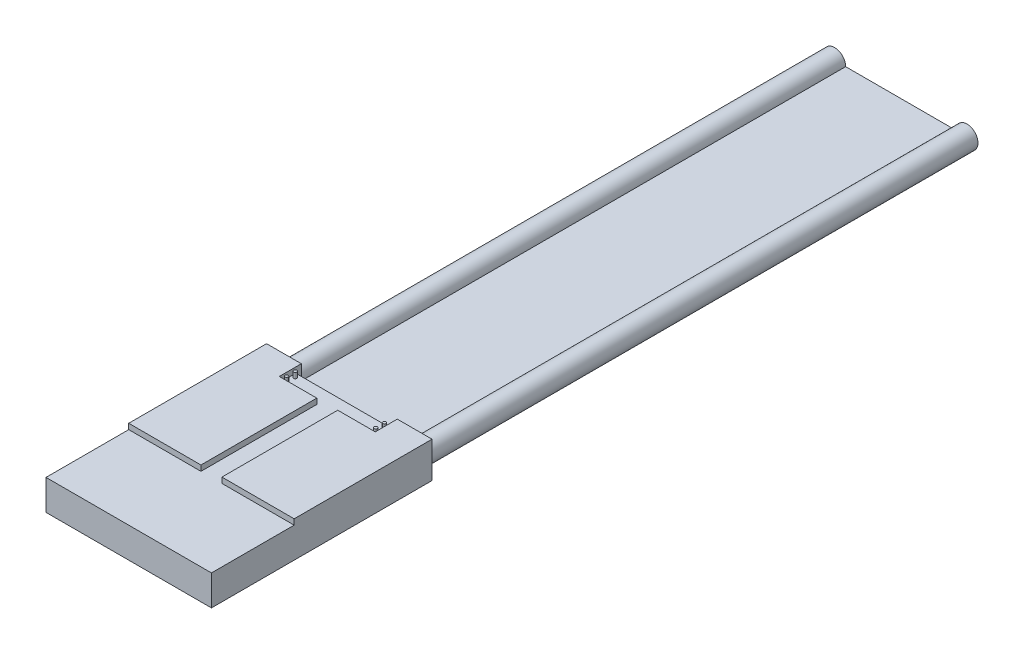
SolidWorks part; units mm, degrees
ref_plane "Front Plane" through (0, 0, 0) normal (0, 0, 1) x (1, 0, 0)
ref_plane "Top Plane" through (0, 0, 0) normal (0, 1, 0) x (1, 0, 0)
ref_plane "Right Plane" through (0, 0, 0) normal (1, 0, 0) x (0, 0, -1)
sketch "Sketch1" plane through (0, 0, 0) normal (0, 0, 1) x (1, 0, 0)
  line L5 (-30, 5.5) -> (0, 5.5)
  line L6 (-30, 5.5) -> (-30, 0)
  line L7 (-30, 0) -> (0, 0)
  line L8 (0, 5.5) -> (0, 0)
  point P4 (0, 0)
  point P5 (0, 0)
  point P6 (-13.0905, 1.99)
  point P8 (-15, 2.013)
  dimension "D1" = 30
  dimension "D2" = 5.5
extrude "Boss-Extrude1" add sketch "Sketch1" against normal blind 25
sketch "Sketch3" plane through (0, 0, -25) normal (0, 0, -1) x (-1, 0, 0)
  line L0 (0, 0) -> (0, 5.5) construction
  line L1 (30, 5.5) -> (30, 0) construction
  line L2 (30, 0) -> (0, 0) construction
  line L4 (3, 2.5) -> (26.9847, 2.5)
  line L5 (3, 2.5) -> (3, 0)
  line L6 (3, 0) -> (26.9847, 0)
  line L7 (26.9847, 2.5) -> (26.9847, 0)
  circle A0 centre (27, 2.5) radius 2
  circle A1 centre (3, 2.5) radius 2
  line M10 (0, 0) -> (30, 0)
  dimension "D1" = 3
  dimension "D6" = 4
  dimension "D2" = 3
  dimension "D3" = 2.5
  dimension "D4" = 2.5
extrude "Boss-Extrude3" add sketch "Sketch3" along normal blind 100 contours L7 A0 L4 | A1 L5 L7 A0 L4 M10 | L4 A1 L5 | L4 A0 L7 | L5 A1 L4 region at (-2.7171, 2.7829, -25) region at (-3.8488, 1.6512, -25) region at (-14.9983, 1.2032, -25) region at (-27.282, 2.7788, -25) region at (-26.1429, 1.6527, -25)
sketch "Sketch5" plane through (0, 5.5, 0) normal (0, 1, 0) x (1, 0, 0)
  line L0 (-30, 25) -> (-30, 0) construction
  line L1 (-6.3, 21) -> (-23.7, 21)
  line L2 (-6.3, 21) -> (-6.3, 24)
  line L3 (-6.3, 24) -> (-23.7, 24)
  line L4 (-23.7, 21) -> (-23.7, 24)
  line L5 (0, 25) -> (0, 0) construction
  line L6 (0, 0) -> (-30, 0) construction
  line L7 (-13.1, 0) -> (-16.9, 0)
  line L8 (-13.1, 0) -> (-13.1, 21)
  line L9 (-13.1, 21) -> (-16.9, 21)
  line L10 (-16.9, 0) -> (-16.9, 21)
  line L11 (0, 25) -> (-30, 25) construction
  line L13 (-6.3, 21) -> (-23.7, 21)
  line L14 (-6.3, 21) -> (-6.3, 25)
  line L15 (-6.3, 25) -> (-23.7, 25)
  line L16 (-23.7, 21) -> (-23.7, 25)
  circle A0 centre (-6.9125, 21.7125) radius 0.2875
  circle A1 centre (-6.9125, 23.2875) radius 0.2875
  circle A2 centre (-6.9125, 23.2875) radius 0.2875
  circle A3 centre (-23.0875, 21.7125) radius 0.2875
  circle A4 centre (-23.0875, 23.2875) radius 0.2875
  point P4 (-23.7, 22.5)
  point P13 (0, 0)
  point P14 (-13.1, -23.2652)
  point P24 (0, 0)
  point P25 (0, 0)
  point P28 (0, 0)
  point P31 (0, 0)
  point P32 (0, 0)
  point P33 (0, 0)
  point P34 (0, 0)
  point P35 (-16.9, 0)
  point P36 (0, 0)
  point P37 (-13.1, 0)
  point P38 (0, 0)
  point P40 (-13.1, 0.0672)
  line M15 (-30, 0) -> (0, 0)
  line M16 (0, 0) -> (0, 25)
  line M17 (0, 25) -> (-30, 25)
  line M18 (-30, 25) -> (-30, 0)
  dimension "D9" = 0.575
  dimension "D10" = 0.6125
  dimension "D12" = 0.575
  dimension "D14" = 0.575
  dimension "D1" = 17.4
  dimension "D2" = 6.3
  dimension "D3" = 6.3
  dimension "D4" = 3
  dimension "D5" = 13.1
  dimension "D6" = 3.8
  dimension "D7" = 13.1
  dimension "D8" = 0.7125
  dimension "D11" = 0.7125
  dimension "D13" = 0.6125
  dimension "D16" = 1
extrude "Boss-Extrude9" add sketch "Sketch5" along normal blind 1 contours L14 L2 L1 L8 M15 M16 M17 | L4 L16 L10 L1 M17 M18 M15 | A3 | A4 | A1 | A0 region at (-6.2647, 5.5, -11.549) region at (-23.7353, 5.5, -11.549) region at (-6.9125, 5.5, -23.2875) region at (-23.0875, 5.5, -21.7125) region at (-23.0875, 5.5, -23.2875)
extrude "Cut-Extrude1" cut sketch "Sketch5<10>" against normal blind 3 contours L16 L3 L14 M17 region at (-15, 5.5, -24.5)
sketch "Sketch5<10>" plane through (0, 5.5, 0) normal (0, 1, 0) x (1, 0, 0) same geometry as "Sketch5"
extrude "Boss-Extrude11" add sketch "Sketch1<5>" along normal blind 15
sketch "Sketch1<5>" plane through (0, 0, 0) normal (0, 0, 1) x (1, 0, 0) same geometry as "Sketch1"
